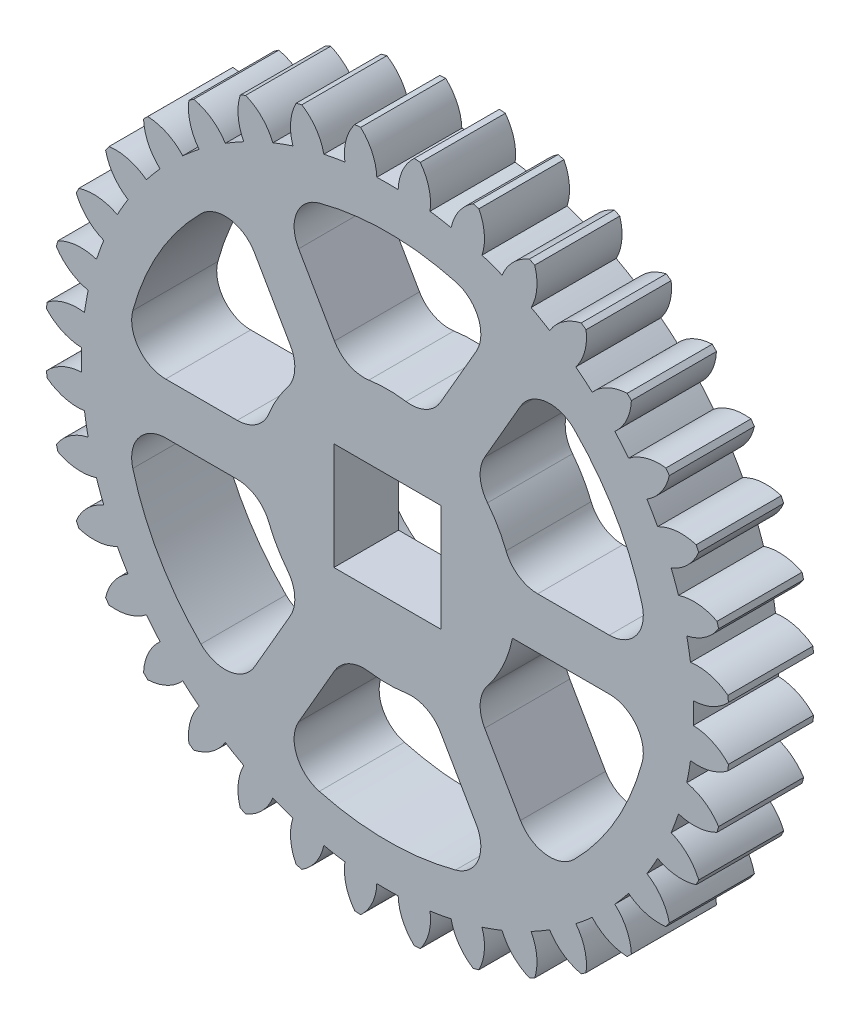
SolidWorks part; units mm, degrees
ref_plane "Front Plane" through (0, 0, 0) normal (0, 0, 1) x (1, 0, 0)
ref_plane "Top Plane" through (0, 0, 0) normal (0, 1, 0) x (1, 0, 0)
ref_plane "Right Plane" through (0, 0, 0) normal (1, 0, 0) x (0, 0, -1)
sketch "Sketch1" plane through (0, 0, 0) normal (0, 0, 1) x (1, 0, 0)
  arc A0 (-19.3729, 5.3726) -> (-19.4637, 5.0337) centre (0, 0) ccw
  arc A1 (-19.4637, 5.0337) -> (-17.593, 3.7395) centre (-16.9795, 6.6255) ccw
  arc A2 (-17.593, 3.7395) -> (-17.811, 2.5032) centre (0, 0) ccw
  arc A3 (-17.811, 2.5032) -> (-20.0115, 1.9269) centre (-18.2216, -0.4186) ccw
  arc A4 (-20.0115, 1.9269) -> (-20.0421, 1.5773) centre (0, 0) ccw
  arc A5 (-20.0421, 1.5773) -> (-17.975, 0.6277) centre (-17.8721, 3.5764) ccw
  arc A6 (-17.975, 0.6277) -> (-17.986, 0) centre (0, 0) ccw
  arc A7 (-17.986, 0) -> (-17.975, -0.6277) centre (0, 0) ccw
  arc A8 (-17.975, -0.6277) -> (-20.0421, -1.5773) centre (-17.8721, -3.5764) ccw
  arc A9 (-20.0421, -1.5773) -> (-20.0115, -1.9269) centre (0, 0) ccw
  arc A10 (-20.0115, -1.9269) -> (-17.811, -2.5032) centre (-18.2216, 0.4186) ccw
  arc A11 (-17.811, -2.5032) -> (-17.593, -3.7395) centre (0, 0) ccw
  arc A12 (-17.593, -3.7395) -> (-19.4637, -5.0337) centre (-16.9795, -6.6255) ccw
  arc A13 (-19.4637, -5.0337) -> (-19.3729, -5.3726) centre (0, 0) ccw
  arc A14 (-19.3729, -5.3726) -> (-17.1057, -5.558) centre (-18.0174, -2.7519) ccw
  arc A15 (-17.1057, -5.558) -> (-16.6763, -6.7377) centre (0, 0) ccw
  arc A16 (-16.6763, -6.7377) -> (-18.294, -8.337) centre (-15.5711, -9.4733) ccw
  arc A17 (-18.294, -8.337) -> (-18.1457, -8.655) centre (0, 0) ccw
  arc A18 (-18.1457, -8.655) -> (-15.8807, -8.4439) centre (-17.2658, -5.8388) ccw
  arc A19 (-15.8807, -8.4439) -> (-15.253, -9.5311) centre (0, 0) ccw
  arc A20 (-15.253, -9.5311) -> (-16.5683, -11.3871) centre (-13.6895, -12.0332) ccw
  arc A21 (-16.5683, -11.3871) -> (-16.3671, -11.6745) centre (0, 0) ccw
  arc A22 (-16.3671, -11.6745) -> (-14.1732, -11.0733) centre (-15.9896, -8.7483) ccw
  arc A23 (-14.1732, -11.0733) -> (-13.3662, -12.035) centre (0, 0) ccw
  arc A24 (-13.3662, -12.035) -> (-14.3393, -14.0911) centre (-11.392, -14.2276) ccw
  arc A25 (-14.3393, -14.0911) -> (-14.0911, -14.3393) centre (0, 0) ccw
  arc A26 (-14.0911, -14.3393) -> (-12.035, -13.3662) centre (-14.2276, -11.392) ccw
  arc A27 (-12.035, -13.3662) -> (-11.0733, -14.1732) centre (0, 0) ccw
  arc A28 (-11.0733, -14.1732) -> (-11.6987, -15.9896) centre (-8.7483, -15.9896) ccw
  arc A29 (-11.6987, -15.9896) -> (-11.6745, -16.3671) centre (-8.7483, -15.9896) ccw
  arc A30 (-11.6745, -16.3671) -> (-11.3871, -16.5683) centre (0, 0) ccw
  arc A31 (-11.3871, -16.5683) -> (-9.5311, -15.253) centre (-12.0332, -13.6895) ccw
  arc A32 (-9.5311, -15.253) -> (-8.4439, -15.8807) centre (0, 0) ccw
  arc A33 (-8.4439, -15.8807) -> (-8.7893, -17.2658) centre (-5.8388, -17.2658) ccw
  arc A34 (-8.7893, -17.2658) -> (-8.655, -18.1457) centre (-5.8388, -17.2658) ccw
  arc A35 (-8.655, -18.1457) -> (-8.337, -18.294) centre (0, 0) ccw
  arc A36 (-8.337, -18.294) -> (-6.7377, -16.6763) centre (-9.4733, -15.5711) ccw
  arc A37 (-6.7377, -16.6763) -> (-5.558, -17.1057) centre (0, 0) ccw
  arc A38 (-5.558, -17.1057) -> (-5.7024, -18.0174) centre (-2.7519, -18.0174) ccw
  arc A39 (-5.7024, -18.0174) -> (-5.3726, -19.3729) centre (-2.7519, -18.0174) ccw
  arc A40 (-5.3726, -19.3729) -> (-5.0337, -19.4637) centre (0, 0) ccw
  arc A41 (-5.0337, -19.4637) -> (-3.7395, -17.593) centre (-6.6255, -16.9795) ccw
  arc A42 (-3.7395, -17.593) -> (-2.5032, -17.811) centre (0, 0) ccw
  arc A43 (-2.5032, -17.811) -> (-2.5319, -18.2216) centre (0.4186, -18.2216) ccw
  arc A44 (-2.5319, -18.2216) -> (-1.9269, -20.0115) centre (0.4186, -18.2216) ccw
  arc A45 (-1.9269, -20.0115) -> (-1.5773, -20.0421) centre (0, 0) ccw
  arc A46 (-1.5773, -20.0421) -> (-0.6277, -17.975) centre (-3.5764, -17.8721) ccw
  arc A47 (-0.6277, -17.975) -> (0.6277, -17.975) centre (0, 0) ccw
  arc A48 (0.6277, -17.975) -> (1.5773, -20.0421) centre (3.5764, -17.8721) ccw
  arc A49 (1.5773, -20.0421) -> (1.9269, -20.0115) centre (0, 0) ccw
  arc A50 (1.9269, -20.0115) -> (2.5032, -17.811) centre (-0.4186, -18.2216) ccw
  arc A51 (2.5032, -17.811) -> (3.7395, -17.593) centre (0, 0) ccw
  arc A52 (3.7395, -17.593) -> (5.0337, -19.4637) centre (6.6255, -16.9795) ccw
  arc A53 (5.0337, -19.4637) -> (5.3726, -19.3729) centre (0, 0) ccw
  arc A54 (5.3726, -19.3729) -> (5.558, -17.1057) centre (2.7519, -18.0174) ccw
  arc A55 (5.558, -17.1057) -> (6.7377, -16.6763) centre (0, 0) ccw
  arc A56 (6.7377, -16.6763) -> (8.337, -18.294) centre (9.4733, -15.5711) ccw
  arc A57 (8.337, -18.294) -> (8.655, -18.1457) centre (0, 0) ccw
  arc A58 (8.655, -18.1457) -> (8.4439, -15.8807) centre (5.8388, -17.2658) ccw
  arc A59 (8.4439, -15.8807) -> (9.5311, -15.253) centre (0, 0) ccw
  arc A60 (9.5311, -15.253) -> (11.3871, -16.5683) centre (12.0332, -13.6895) ccw
  arc A61 (11.3871, -16.5683) -> (11.6745, -16.3671) centre (0, 0) ccw
  arc A62 (11.6745, -16.3671) -> (11.0733, -14.1732) centre (8.7483, -15.9896) ccw
  arc A63 (11.0733, -14.1732) -> (12.035, -13.3662) centre (0, 0) ccw
  arc A64 (12.035, -13.3662) -> (14.0911, -14.3393) centre (14.2276, -11.392) ccw
  arc A65 (14.0911, -14.3393) -> (14.3393, -14.0911) centre (0, 0) ccw
  arc A66 (14.3393, -14.0911) -> (13.3662, -12.035) centre (11.392, -14.2276) ccw
  arc A67 (13.3662, -12.035) -> (14.1732, -11.0733) centre (0, 0) ccw
  arc A68 (14.1732, -11.0733) -> (16.3671, -11.6745) centre (15.9896, -8.7483) ccw
  arc A69 (16.3671, -11.6745) -> (16.5683, -11.3871) centre (0, 0) ccw
  arc A70 (16.5683, -11.3871) -> (15.253, -9.5311) centre (13.6895, -12.0332) ccw
  arc A71 (15.253, -9.5311) -> (15.8807, -8.4439) centre (0, 0) ccw
  arc A72 (15.8807, -8.4439) -> (18.1457, -8.655) centre (17.2658, -5.8388) ccw
  arc A73 (18.1457, -8.655) -> (18.294, -8.337) centre (0, 0) ccw
  arc A74 (18.294, -8.337) -> (16.6763, -6.7377) centre (15.5711, -9.4733) ccw
  arc A75 (16.6763, -6.7377) -> (17.1057, -5.558) centre (0, 0) ccw
  arc A76 (17.1057, -5.558) -> (19.3729, -5.3726) centre (18.0174, -2.7519) ccw
  arc A77 (19.3729, -5.3726) -> (19.4637, -5.0337) centre (0, 0) ccw
  arc A78 (19.4637, -5.0337) -> (17.593, -3.7395) centre (16.9795, -6.6255) ccw
  arc A79 (17.593, -3.7395) -> (17.811, -2.5032) centre (0, 0) ccw
  arc A80 (17.811, -2.5032) -> (20.0115, -1.9269) centre (18.2216, 0.4186) ccw
  arc A81 (20.0115, -1.9269) -> (20.0421, -1.5773) centre (0, 0) ccw
  arc A82 (20.0421, -1.5773) -> (17.975, -0.6277) centre (17.8721, -3.5764) ccw
  arc A83 (17.975, -0.6277) -> (17.975, 0.6277) centre (0, 0) ccw
  arc A84 (17.975, 0.6277) -> (20.0421, 1.5773) centre (17.8721, 3.5764) ccw
  arc A85 (20.0421, 1.5773) -> (20.0115, 1.9269) centre (0, 0) ccw
  arc A86 (20.0115, 1.9269) -> (17.811, 2.5032) centre (18.2216, -0.4186) ccw
  arc A87 (17.811, 2.5032) -> (17.593, 3.7395) centre (0, 0) ccw
  arc A88 (17.593, 3.7395) -> (19.4637, 5.0337) centre (16.9795, 6.6255) ccw
  arc A89 (19.4637, 5.0337) -> (19.3729, 5.3726) centre (0, 0) ccw
  arc A90 (19.3729, 5.3726) -> (17.1057, 5.558) centre (18.0174, 2.7519) ccw
  arc A91 (17.1057, 5.558) -> (16.6763, 6.7377) centre (0, 0) ccw
  arc A92 (16.6763, 6.7377) -> (18.294, 8.337) centre (15.5711, 9.4733) ccw
  arc A93 (18.294, 8.337) -> (18.1457, 8.655) centre (0, 0) ccw
  arc A94 (18.1457, 8.655) -> (15.8807, 8.4439) centre (17.2658, 5.8388) ccw
  arc A95 (15.8807, 8.4439) -> (15.253, 9.5311) centre (0, 0) ccw
  arc A96 (15.253, 9.5311) -> (16.5683, 11.3871) centre (13.6895, 12.0332) ccw
  arc A97 (16.5683, 11.3871) -> (16.3671, 11.6745) centre (0, 0) ccw
  arc A98 (16.3671, 11.6745) -> (14.1732, 11.0733) centre (15.9896, 8.7483) ccw
  arc A99 (14.1732, 11.0733) -> (13.3662, 12.035) centre (0, 0) ccw
  arc A100 (13.3662, 12.035) -> (14.3393, 14.0911) centre (11.392, 14.2276) ccw
  arc A101 (14.3393, 14.0911) -> (14.0911, 14.3393) centre (0, 0) ccw
  arc A102 (14.0911, 14.3393) -> (12.035, 13.3662) centre (14.2276, 11.392) ccw
  arc A103 (12.035, 13.3662) -> (11.0733, 14.1732) centre (0, 0) ccw
  arc A104 (11.0733, 14.1732) -> (11.6745, 16.3671) centre (8.7483, 15.9896) ccw
  arc A105 (11.6745, 16.3671) -> (11.3871, 16.5683) centre (0, 0) ccw
  arc A106 (11.3871, 16.5683) -> (9.5311, 15.253) centre (12.0332, 13.6895) ccw
  arc A107 (9.5311, 15.253) -> (8.4439, 15.8807) centre (0, 0) ccw
  arc A108 (8.4439, 15.8807) -> (8.655, 18.1457) centre (5.8388, 17.2658) ccw
  arc A109 (8.655, 18.1457) -> (8.337, 18.294) centre (0, 0) ccw
  arc A110 (8.337, 18.294) -> (6.7377, 16.6763) centre (9.4733, 15.5711) ccw
  arc A111 (6.7377, 16.6763) -> (5.558, 17.1057) centre (0, 0) ccw
  arc A112 (5.558, 17.1057) -> (5.3726, 19.3729) centre (2.7519, 18.0174) ccw
  arc A113 (5.3726, 19.3729) -> (5.0337, 19.4637) centre (0, 0) ccw
  arc A114 (5.0337, 19.4637) -> (3.7395, 17.593) centre (6.6255, 16.9795) ccw
  arc A115 (3.7395, 17.593) -> (2.5032, 17.811) centre (0, 0) ccw
  arc A116 (2.5032, 17.811) -> (1.9269, 20.0115) centre (-0.4186, 18.2216) ccw
  arc A117 (1.9269, 20.0115) -> (1.5773, 20.0421) centre (0, 0) ccw
  arc A118 (1.5773, 20.0421) -> (0.6277, 17.975) centre (3.5764, 17.8721) ccw
  arc A119 (0.6277, 17.975) -> (-0.6277, 17.975) centre (0, 0) ccw
  arc A120 (-0.6277, 17.975) -> (-1.5773, 20.0421) centre (-3.5764, 17.8721) ccw
  arc A121 (-1.5773, 20.0421) -> (-1.9269, 20.0115) centre (0, 0) ccw
  arc A122 (-1.9269, 20.0115) -> (-2.5319, 18.2216) centre (0.4186, 18.2216) ccw
  arc A123 (-2.5319, 18.2216) -> (-2.5032, 17.811) centre (0.4186, 18.2216) ccw
  arc A124 (-2.5032, 17.811) -> (-3.7395, 17.593) centre (0, 0) ccw
  arc A125 (-3.7395, 17.593) -> (-5.0337, 19.4637) centre (-6.6255, 16.9795) ccw
  arc A126 (-5.0337, 19.4637) -> (-5.3726, 19.3729) centre (0, 0) ccw
  arc A127 (-5.3726, 19.3729) -> (-5.7024, 18.0174) centre (-2.7519, 18.0174) ccw
  arc A128 (-5.7024, 18.0174) -> (-5.558, 17.1057) centre (-2.7519, 18.0174) ccw
  arc A129 (-5.558, 17.1057) -> (-6.7377, 16.6763) centre (0, 0) ccw
  arc A130 (-6.7377, 16.6763) -> (-8.337, 18.294) centre (-9.4733, 15.5711) ccw
  arc A131 (-8.337, 18.294) -> (-8.655, 18.1457) centre (0, 0) ccw
  arc A132 (-8.655, 18.1457) -> (-8.7893, 17.2658) centre (-5.8388, 17.2658) ccw
  arc A133 (-8.7893, 17.2658) -> (-8.4439, 15.8807) centre (-5.8388, 17.2658) ccw
  arc A134 (-8.4439, 15.8807) -> (-9.5311, 15.253) centre (0, 0) ccw
  arc A135 (-9.5311, 15.253) -> (-11.3871, 16.5683) centre (-12.0332, 13.6895) ccw
  arc A136 (-11.3871, 16.5683) -> (-11.6745, 16.3671) centre (0, 0) ccw
  arc A137 (-11.6745, 16.3671) -> (-11.6987, 15.9896) centre (-8.7483, 15.9896) ccw
  arc A138 (-11.6987, 15.9896) -> (-11.0733, 14.1732) centre (-8.7483, 15.9896) ccw
  arc A139 (-11.0733, 14.1732) -> (-12.035, 13.3662) centre (0, 0) ccw
  arc A140 (-12.035, 13.3662) -> (-14.0911, 14.3393) centre (-14.2276, 11.392) ccw
  arc A141 (-14.0911, 14.3393) -> (-14.3393, 14.0911) centre (0, 0) ccw
  arc A142 (-14.3393, 14.0911) -> (-13.3662, 12.035) centre (-11.392, 14.2276) ccw
  arc A143 (-13.3662, 12.035) -> (-14.1732, 11.0733) centre (0, 0) ccw
  arc A144 (-14.1732, 11.0733) -> (-16.3671, 11.6745) centre (-15.9896, 8.7483) ccw
  arc A145 (-16.3671, 11.6745) -> (-16.5683, 11.3871) centre (0, 0) ccw
  arc A146 (-16.5683, 11.3871) -> (-15.253, 9.5311) centre (-13.6895, 12.0332) ccw
  arc A147 (-15.253, 9.5311) -> (-15.8807, 8.4439) centre (0, 0) ccw
  arc A148 (-15.8807, 8.4439) -> (-18.1457, 8.655) centre (-17.2658, 5.8388) ccw
  arc A149 (-18.1457, 8.655) -> (-18.294, 8.337) centre (0, 0) ccw
  arc A150 (-18.294, 8.337) -> (-16.6763, 6.7377) centre (-15.5711, 9.4733) ccw
  arc A151 (-16.6763, 6.7377) -> (-17.1057, 5.558) centre (0, 0) ccw
  arc A152 (-17.1057, 5.558) -> (-19.3729, 5.3726) centre (-18.0174, 2.7519) ccw
extrude "Boss-Extrude1" add sketch "Sketch1" along normal blind 5
sketch "Sketch2" plane through (0, 0, 0) normal (0, 0, -1) x (-1, 0, 0)
  line L1 (-3.15, 3.15) -> (3.15, 3.15)
  line L2 (-3.15, 3.15) -> (-3.15, -3.15)
  line L3 (-3.15, -3.15) -> (3.15, -3.15)
  line L4 (3.15, 3.15) -> (3.15, -3.15)
  line L5 (-3.15, 3.15) -> (3.15, -3.15) construction
  line L6 (-3.15, -3.15) -> (3.15, 3.15) construction
  circle A0 centre (0, 0) radius 5.5
  point P0 (0, 0)
  dimension "D3" = 11
  dimension "D1" = 6.3
  dimension "D2" = 6.3
extrude "Cut-Extrude1" cut sketch "Sketch2" against normal blind 5 contours L4 L1 L2 L3 region at (0, 0, 0)
extrude "Cut-Extrude2" cut sketch "Sketch2<3>" against normal blind 1.2
sketch "Sketch2<3>" plane through (0, 0, 0) normal (0, 0, -1) x (-1, 0, 0) same geometry as "Sketch2"
sketch "Sketch3" plane through (0, 0, 0) normal (0, 0, -1) x (-1, 0, 0)
  line L0 (-7.3485, 1.5) -> (-15.4272, 1.5)
  line L1 (-15.4272, -1.5) -> (-7.3485, -1.5)
  line L2 (-2.3752, 7.114) -> (-6.4146, 14.1104)
  line L3 (-9.0127, 12.6104) -> (-4.9733, 5.614)
  line L4 (4.9733, 5.614) -> (9.0127, 12.6104)
  line L5 (6.4146, 14.1104) -> (2.3752, 7.114)
  line L6 (7.3485, -1.5) -> (15.4272, -1.5)
  line L7 (15.4272, 1.5) -> (7.3485, 1.5)
  line L8 (2.3752, -7.114) -> (6.4146, -14.1104)
  line L9 (9.0127, -12.6104) -> (4.9733, -5.614)
  line L10 (-4.9733, -5.614) -> (-9.0127, -12.6104)
  line L11 (-6.4146, -14.1104) -> (-2.3752, -7.114)
  line L12 (0, 0) -> (-15.5, 0) construction
  circle A0 centre (0, 0) radius 7.5
  circle A1 centre (0, 0) radius 15.5
  dimension "D1" = 31
  dimension "D2" = 15
  dimension "D3" = 3
  dimension "D5" = 6
extrude "Cut-Extrude3" cut sketch "Sketch3" against normal up to next contours L3 A1 L0 A0 | L5 A1 L2 A0 | L7 A1 L4 A0 | L9 A1 L6 A0 | L11 A1 L8 A0 | L1 A1 L10 A0 region at (10.2177, 5.8992, 0) region at (10.2177, -5.8992, 0) region at (0, 11.7984, 0) region at (0, -11.7984, 0) region at (-10.2177, 5.8992, 0) region at (-10.2177, -5.8992, 0)
fillet "Fillet1" radius 2 23 edges at (15.4272, -1.5, 2.5) (9.0127, -12.6104, 2.5) (4.9733, -5.614, 2.5) (2.3752, -7.114, 2.5) (6.4146, -14.1104, 2.5) (-6.4146, -14.1104, 2.5) (-2.3752, -7.114, 2.5) (-4.9733, -5.614, 2.5) (-9.0127, -12.6104, 2.5) (-15.4272, -1.5, 2.5) (-7.3485, -1.5, 2.5) (-7.3485, 1.5, 2.5) (-15.4272, 1.5, 2.5) (-9.0127, 12.6104, 2.5) (-4.9733, 5.614, 2.5) (-6.4146, 14.1104, 2.5) (6.4146, 14.1104, 2.5) (2.3752, 7.114, 2.5) (4.9733, 5.614, 2.5) (7.3485, 1.5, 2.5) (15.4272, 1.5, 2.5) (9.0127, 12.6104, 2.5) (-2.3752, 7.114, 2.5)
